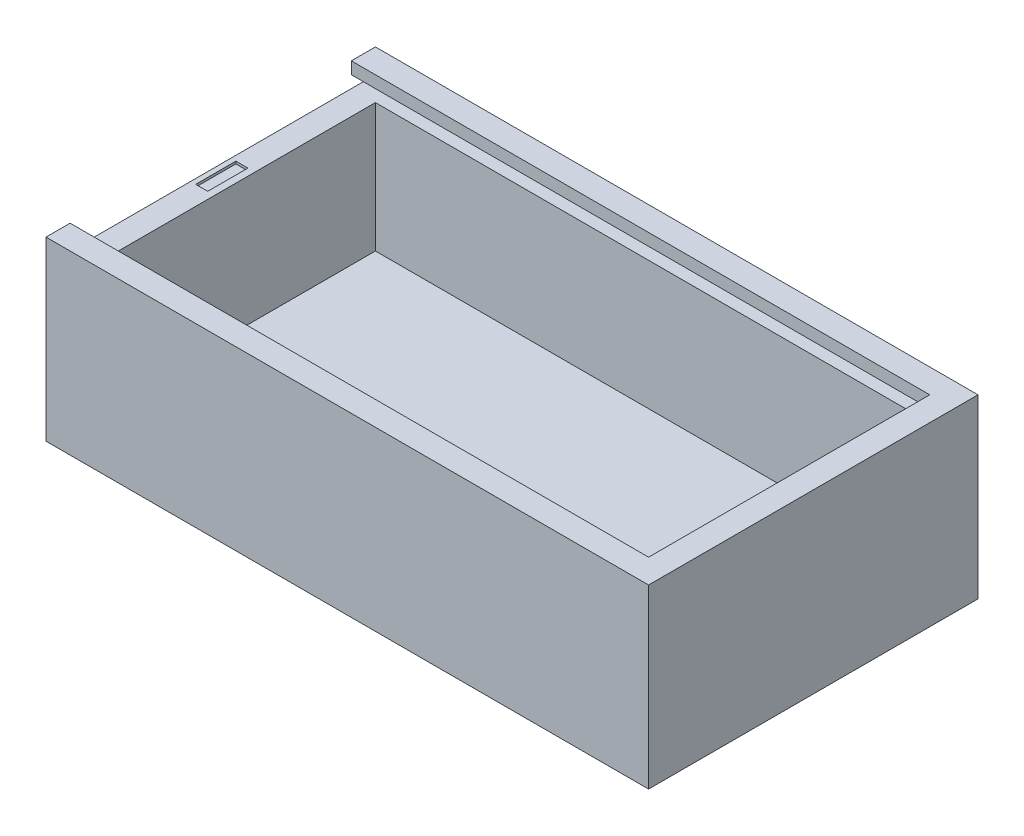
SolidWorks part; units mm, degrees
ref_plane "Front Plane" through (0, 0, 0) normal (0, 0, 1) x (1, 0, 0)
ref_plane "Top Plane" through (0, 0, 0) normal (0, 1, 0) x (1, 0, 0)
ref_plane "Right Plane" through (0, 0, 0) normal (1, 0, 0) x (0, 0, -1)
sketch "Croquis1" plane through (0, 0, 0) normal (0, 1, 0) x (1, 0, 0)
  line L0 (34.5, -17.5) -> (34.5, 17.5)
  line L1 (-37.5, 20.5) -> (37.5, 20.5)
  line L2 (-37.5, 20.5) -> (-37.5, -20.5)
  line L3 (-37.5, -20.5) -> (37.5, -20.5)
  line L4 (37.5, 20.5) -> (37.5, -20.5)
  line L5 (34.5, -17.5) -> (-34.5, -17.5)
  line L6 (34.5, 17.5) -> (-34.5, 17.5)
  line L7 (-34.5, -17.5) -> (-34.5, 17.5)
  line L8 (34.5, -17.5) -> (-34.5, 17.5) construction
  line L9 (34.5, 17.5) -> (-34.5, -17.5) construction
  point P4 (0, 20.5)
  point P6 (-37.5, 0)
  point P8 (0, 0)
  dimension "D1" = 75
  dimension "D2" = 41
  dimension "D3" = 3
  dimension "D4" = 3
extrude "Saliente-Extruir1" add sketch "Croquis1" along normal blind 22
extrude "Saliente-Extruir2" add sketch "Croquis1<2>" along normal blind 3 contours L7 L5 L0 L6 region at (0, 0, 0)
sketch "Croquis1<2>" plane through (0, 0, 0) normal (0, 1, 0) x (1, 0, 0) same geometry as "Croquis1"
sketch "Croquis3" plane through (-37.5, 0, 0) normal (-1, 0, 0) x (0, 0, 1)
  line L0 (-17.5, 22) -> (-17.5, 19)
  line L1 (-20.5, 22) -> (20.5, 22) construction
  line L2 (-17.5, 19) -> (17.5, 19)
  line L3 (17.5, 19) -> (17.5, 22)
  line L4 (-17.5, 22) -> (17.5, 22)
  line L5 (-20.5, 22) -> (-20.5, 0) construction
  line L6 (20.5, 22) -> (20.5, 0) construction
  line L7 (-17.5, 20.5) -> (-19, 20.5)
  line L8 (-19, 20.5) -> (-19, 19)
  line L9 (-19, 19) -> (-17.5, 19)
  line L10 (17.5, 20.5) -> (19, 20.5)
  line L11 (19, 20.5) -> (19, 19)
  line L12 (19, 19) -> (17.5, 19)
  line M7 (20.5, 22) -> (-20.5, 22)
  dimension "D1" = 3
  dimension "D2" = 3
  dimension "D3" = 3
  dimension "D4" = 1.5
  dimension "D5" = 1.5
extrude "Cortar-Extruir1" cut sketch "Croquis3" against normal blind 72 contours L2 L3 L0 M7 | L8 L9 L0 L7 | L12 L11 L10 L3 region at (-37.5, 20.5, 0) region at (-37.5, 19.75, -18.25) region at (-37.5, 19.75, 18.25)
sketch "Croquis4" plane through (34.5, 0, 0) normal (-1, 0, 0) x (0, 0, 1)
  line L0 (-19, 19) -> (-19, 20.5)
  line L1 (-19, 20.5) -> (19, 20.5)
  line L2 (19, 20.5) -> (19, 19)
  line L3 (19, 19) -> (-19, 19)
extrude "Cortar-Extruir2" cut sketch "Croquis4" against normal blind 1.5
sketch "Croquis7" plane through (0, 19, 0) normal (0, 1, 0) x (1, 0, 0)
  line L0 (-37.7424, 0) -> (-34.5, 0) construction
  line L1 (-34.5, -17.5) -> (-34.5, 17.5) construction
  line L2 (-36.8712, -2.5) -> (-35.3712, -2.5)
  line L3 (-36.8712, -2.5) -> (-36.8712, 2.5)
  line L4 (-35.3712, -2.5) -> (-35.3712, 2.5)
  line L5 (-36.8712, 2.5) -> (-35.3712, 2.5)
  line L6 (-36.8712, -2.5) -> (-35.3712, 2.5) construction
  line L7 (-35.3712, -2.5) -> (-36.8712, 2.5) construction
  line L8 (-37.5, 19) -> (-37.5, -19) construction
  point P5 (-36.1212, 0)
  point P6 (-36.1212, 0)
  dimension "D1" = 1.5
  dimension "D2" = 5
  dimension "D3" = 0.6288
extrude "Cortar-Extruir3" cut sketch "Croquis7" against normal blind 0.3
